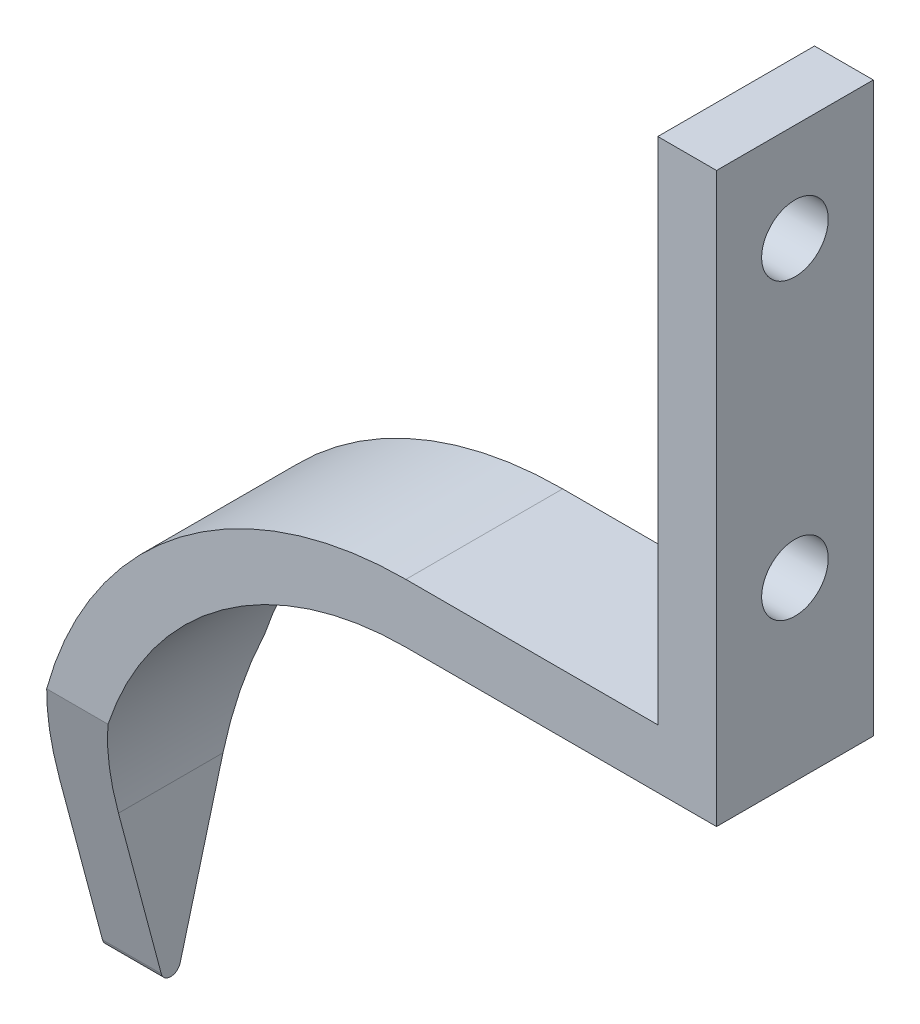
SolidWorks part; units mm, degrees
ref_plane "Front" through (0, 0, 0) normal (0, 0, 1) x (1, 0, 0)
ref_plane "Top" through (0, 0, 0) normal (0, 1, 0) x (1, 0, 0)
ref_plane "Right" through (0, 0, 0) normal (1, 0, 0) x (0, 0, -1)
ref_plane "Plane1" through (0, 0, 0) normal (0, 0, -1) x (-1, 0, 0)
sketch "Sketch1" plane through (0, 0, 0) normal (0, 0, -1) x (-1, 0, 0)
  line L1 (24.145, 100) -> (24.145, 27.967) construction
  line L2 (24.145, 100) -> (24.145, 71)
  line L3 (24.145, 71) -> (40, 71)
  line L7 (27.145, 68) -> (40, 68) construction
  line L8 (-17.145, 68) -> (17.145, 68) construction
  line L9 (-40, 68) -> (-27.145, 68) construction
  line L11 (53, 36.8203) -> (53, -69.4315) construction
  line L12 (40, 74) -> (27.145, 74)
  line L13 (27.145, 74) -> (27.145, 100)
  line L14 (27.145, 100) -> (24.145, 100)
  line L15 (56, 55) -> (56, 45)
  line L16 (56, 45) -> (59, 45)
  line L17 (59, 45) -> (59, 55)
  arc A1 (53, 55) -> (40, 68) centre (40, 55) ccw construction
  arc A2 (56, 55) -> (40, 71) centre (40, 55) ccw
  arc A3 (59, 55) -> (40, 74) centre (40, 55) ccw
  point P10 (32.0725, 71)
  dimension "D1" = 3
  dimension "D4" = 3
  dimension "D5" = 10
  dimension "D2" = 3
  dimension "D3" = 3
extrude "Boss-Extrude1" add sketch "Sketch1" along normal mid plane 8 contours L17 A3 L12 L13 L14 L2 L3 A2 L15 L16 region at (-39.7867, 72.222, 0)
sketch "Sketch2" plane through (-59, 0, 0) normal (-1, 0, 0) x (0, 0, 1)
  line L0 (4, 55) -> (4, 74) construction
  line L1 (-4, 74) -> (-4, 55) construction
  line L2 (4, 45) -> (4, 55) construction
  line L3 (-4, 45) -> (4, 45) construction
  line L4 (-4, 45) -> (-4, 55) construction
  line L5 (4, 55) -> (4, 74)
  line L6 (-4, 74) -> (-4, 55)
  line L7 (4, 45) -> (4, 55)
  line L8 (-4, 45) -> (4, 45)
  line L9 (-4, 45) -> (-4, 55)
  line L10 (0, 45) -> (-4, 60)
  line L11 (-4, 60) -> (4, 60)
  line L12 (4, 60) -> (0, 45)
  point P8 (0, 0)
  line M6 (4, 45) -> (4, 55)
  line M7 (4, 55) -> (-4, 55)
  line M8 (-4, 55) -> (-4, 45)
  line M9 (-4, 45) -> (4, 45)
  dimension "D1" = 15
extrude "Cut-Extrude1" cut sketch "Sketch2" against normal through all contours L10 M9 M7 M8 | L10 L6 M7 | L12 L8 M7 M6 | L5 L12 M7 region at (-59, 56.6667, 3.5556) region at (-59, 49.1667, 2.5556) region at (-59, 56.6667, -3.5556) region at (-59, 49.1667, -2.5556)
fillet "Fillet1" radius 0.5 1 edges at (-57.5, 45, 0)
sketch "Sketch3" plane through (-27.145, 0, 0) normal (-1, 0, 0) x (0, 0, 1)
  line L4 (4, 74) -> (4, 100)
  line L5 (4, 100) -> (-4, 100)
  line L6 (-4, 100) -> (-4, 74)
  line L7 (-4, 74) -> (4, 74)
  line L8 (4, 74) -> (4, 100)
  line L9 (4, 100) -> (-4, 100)
  line L10 (-4, 100) -> (-4, 74)
  line L11 (-4, 74) -> (4, 74)
  circle A0 centre (0, 80) radius 1.7 construction
  circle A1 centre (0, 80) radius 1.7
  circle A2 centre (0, 95) radius 1.7 construction
  circle A3 centre (0, 95) radius 1.7
  dimension "D1" = 0
extrude "Cut-Extrude2" cut sketch "Sketch3" against normal through all contours A1 | A3 region at (-27.145, 80, 0)
